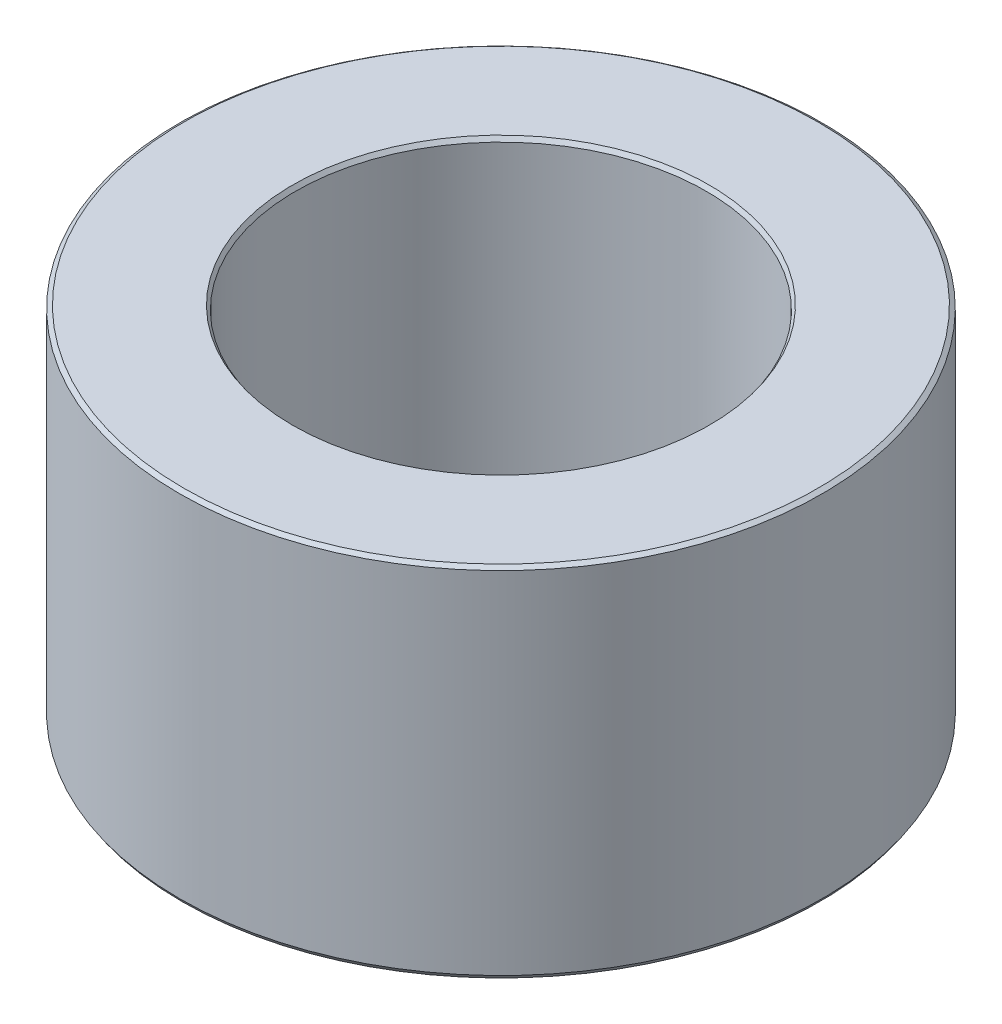
SolidWorks part; units mm, degrees
ref_plane "Front Plane" through (0, 0, 0) normal (0, 0, 1) x (1, 0, 0)
ref_plane "Top Plane" through (0, 0, 0) normal (0, 1, 0) x (1, 0, 0)
ref_plane "Right Plane" through (0, 0, 0) normal (1, 0, 0) x (0, 0, -1)
sketch "Sketch1" plane through (0, 0, 0) normal (0, 1, 0) x (1, 0, 0)
  circle A0 centre (0, 0) radius 42.5
  dimension "SLEEVE_OD" = 85
extrude "Boss-Extrude1" add sketch "Sketch1" along normal blind 47.2961
sketch "Sketch2" plane through (0, 0, 0) normal (0, 1, 0) x (1, 0, 0)
  circle A0 centre (0, 0) radius 27.1818
  dimension "BORE_D" = 54.3635
extrude "Cut-Extrude1" cut sketch "Sketch2" along normal through all
chamfer "Chamfer1" distance 0.3651 angle 56.168 4 edges at (0, 47.2961, 27.1818) (0, 0, 27.1818) (0, 0, 42.5) (0, 47.2961, 42.5) first distance on face at (0, 47.2961, 27.1818) first distance on face at (0, 0, 27.1818) first distance on face at (0, 47.2961, 42.5)
